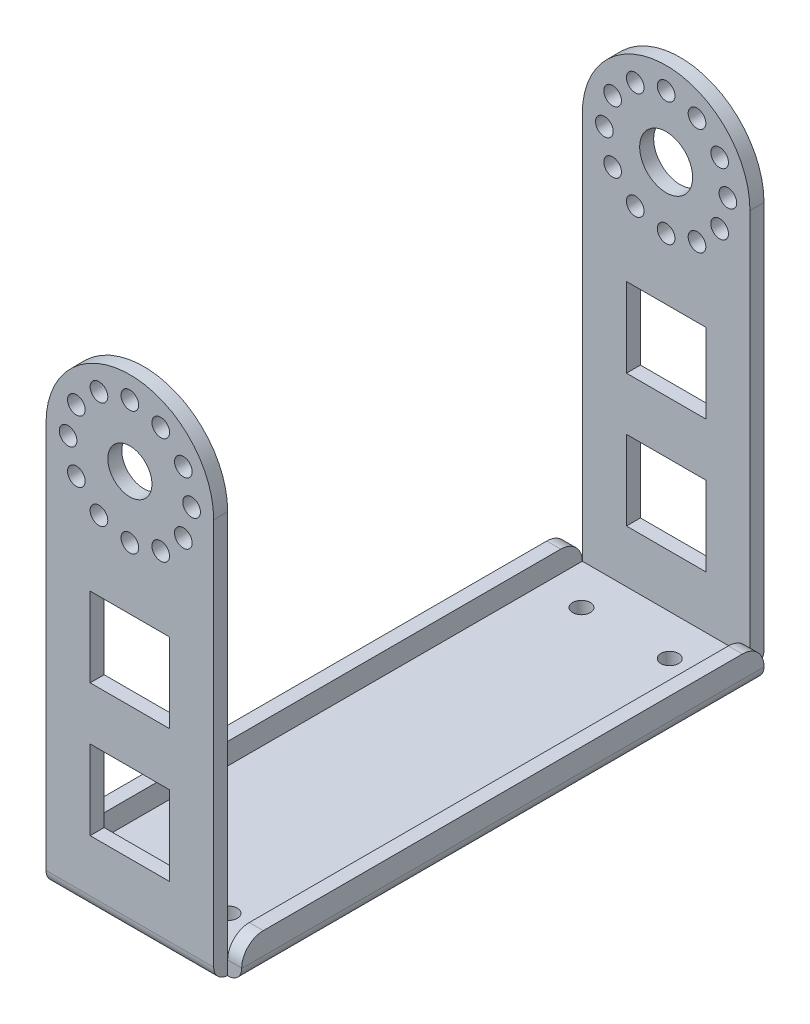
SolidWorks part; units mm, degrees
ref_plane "Plan de face" through (0, 0, 0) normal (0, 0, 1) x (1, 0, 0)
ref_plane "Plan de dessus" through (0, 0, 0) normal (0, 1, 0) x (1, 0, 0)
ref_plane "Plan de droite" through (0, 0, 0) normal (1, 0, 0) x (0, 0, -1)
sketch "Esquisse1" plane through (0, 0, 0) normal (0, 1, 0) x (1, 0, 0)
  line L1 (-9.5, -29.5938) -> (9.5, -29.5938)
  line L2 (-9.5, -29.5938) -> (-9.5, 29.5937)
  line L3 (-9.5, 29.5937) -> (9.5, 29.5937)
  line L4 (9.5, -29.5938) -> (9.5, 29.5937)
  line L5 (-9.5, -29.5938) -> (9.5, 29.5937) construction
  line L6 (-9.5, 29.5937) -> (9.5, -29.5938) construction
  point P0 (0, 0)
  dimension "D1" = 59.1875
  dimension "D2" = 19
extrude "Boss.-Extru.1" add sketch "Esquisse1" along normal blind 1.5875
sketch "Esquisse3" plane through (9.5, 0, 0) normal (1, 0, 0) x (0, 0, -1)
  line L1 (-29.5938, 0) -> (29.5937, 0)
  line L2 (-29.5938, 0) -> (-29.5938, 4)
  line L3 (-29.5938, 4) -> (29.5937, 4)
  line L4 (29.5937, 0) -> (29.5937, 4)
  dimension "D1" = 59.1875
  dimension "D2" = 4
extrude "Boss.-Extru.2" add sketch "Esquisse3" along normal blind 1.5875
sketch "Esquisse4" plane through (-9.5, 0, 0) normal (-1, 0, 0) x (0, 0, 1)
  line L1 (-29.5937, 0) -> (29.5938, 0)
  line L2 (-29.5937, 0) -> (-29.5937, 4)
  line L3 (-29.5937, 4) -> (29.5938, 4)
  line L4 (29.5938, 0) -> (29.5938, 4)
  dimension "D1" = 59.1875
  dimension "D2" = 4
extrude "Boss.-Extru.3" add sketch "Esquisse4" along normal blind 1.5875
fillet "Congé1" radius 1.5 1 edges at (11.0875, 0, 0)
fillet "Congé2" radius 1.5 1 edges at (-11.0875, 0, 0)
sketch "Esquisse5" plane through (0, 0, 29.5938) normal (0, 0, 1) x (1, 0, 0)
  line L1 (-9.5, 0.043) -> (9.5, 0.043)
  line L2 (-9.5, 0.043) -> (-9.5, 45.543)
  line L3 (-9.5, 45.543) -> (9.5, 45.543) construction
  line L4 (9.5, 0.043) -> (9.5, 45.543)
  circle A0 centre (0, 45.543) radius 2.5
  arc A1 (-9.5, 45.543) -> (9.5, 45.543) centre (0, 45.543) cw
  circle A2 centre (0, 45.543) radius 7 construction
  circle A3 centre (0, 38.543) radius 1
  circle A4 centre (-3.5, 39.4808) radius 1
  circle A5 centre (-6.0622, 42.043) radius 1
  circle A6 centre (-7, 45.543) radius 1
  circle A7 centre (-6.0622, 49.043) radius 1
  circle A8 centre (-3.5, 51.6052) radius 1
  circle A9 centre (0, 52.543) radius 1
  circle A10 centre (3.5, 51.6052) radius 1
  circle A11 centre (6.0622, 49.043) radius 1
  circle A12 centre (7, 45.543) radius 1
  circle A13 centre (6.0622, 42.043) radius 1
  circle A14 centre (3.5, 39.4808) radius 1
  point P33 (0, 45.543)
  dimension "D3" = 9.5
  dimension "D4" = 5
  dimension "D1" = 19
  dimension "D2" = 45.5
extrude "Boss.-Extru.8" add sketch "Esquisse5" along normal blind 1.5875 separate body
fillet "Congé3" radius 1.5875 3 edges at (0, 0.043, 31.1813) (9.5, 0.043, 30.3875) (-9.5, 0.043, 30.3875)
sketch "Esquisse8" plane through (0, 0, -29.5937) normal (0, 0, -1) x (-1, 0, 0)
  line L0 (-9.5875, 0) -> (9.5875, 0) construction
  line L1 (-9.5, 0) -> (9.5047, 0)
  line L2 (-9.5, 0) -> (-9.5, 45.5)
  line L3 (-9.5, 45.5) -> (9.5047, 45.5) construction
  line L4 (9.5047, 0) -> (9.5047, 45.5)
  arc A0 (9.5047, 45.5) -> (-9.5, 45.5) centre (0.0024, 45.5) ccw
  circle A1 centre (0.0024, 45.5) radius 3
  circle A2 centre (0.0024, 45.5) radius 7 construction
  circle A3 centre (0.0024, 38.5) radius 1
  circle A4 centre (-3.4976, 39.4378) radius 1
  circle A5 centre (-6.0598, 42) radius 1
  circle A6 centre (-6.9976, 45.5) radius 1
  circle A7 centre (-6.0598, 49) radius 1
  circle A8 centre (-3.4976, 51.5622) radius 1
  circle A9 centre (0.0024, 52.5) radius 1
  circle A10 centre (3.5024, 51.5622) radius 1
  circle A11 centre (6.0645, 49) radius 1
  circle A12 centre (7.0024, 45.5) radius 1
  circle A13 centre (6.0645, 42) radius 1
  circle A14 centre (3.5024, 39.4378) radius 1
  point P36 (0.0024, 45.5)
  dimension "D3" = 9.5024
  dimension "D1" = 19.0047
  dimension "D2" = 45.5
extrude "Boss.-Extru.10" add sketch "Esquisse8" along normal blind 1.5875 separate body
fillet "Congé4" radius 1.5875 3 edges at (-0.0024, 0, -31.1812) (-9.5047, 0, -30.3875) (9.5, 0, -30.3875)
sketch "Esquisse9" plane through (0, 1.5875, 0) normal (0, 1, 0) x (1, 0, 0)
  line L0 (0, -25) -> (0, -29.5938) construction
  line L1 (5, 25) -> (-5, 25) construction
  line L2 (5, 25) -> (5, -25) construction
  line L3 (5, -25) -> (-5, -25) construction
  line L4 (-5, 25) -> (-5, -25) construction
  line L5 (5, 25) -> (-5, -25) construction
  line L6 (5, -25) -> (-5, 25) construction
  line L7 (-9.5, -29.5938) -> (9.5, -29.5938) construction
  line L8 (-5, -3.1455) -> (-9.5, -3.1455) construction
  line L9 (-9.5, 29.5937) -> (-9.5, -29.5938) construction
  line L10 (5, -3.1455) -> (9.5, -3.1455) construction
  line L11 (9.5, -29.5938) -> (9.5, 29.5937) construction
  line L12 (0, 25) -> (0, 29.5937) construction
  line L13 (9.5, 29.5937) -> (-9.5, 29.5937) construction
  circle A0 centre (-5, 25) radius 1
  circle A1 centre (5, 25) radius 1
  circle A2 centre (-5, -25) radius 1
  circle A3 centre (5, -25) radius 1
  point P0 (0, 0)
  dimension "D3" = 2
  dimension "D1" = 50
  dimension "D2" = 10
extrude "Enlèv. mat.-Extru.1" cut sketch "Esquisse9" against normal blind 1.5875
sketch "Esquisse10" plane through (0, 0, 31.1813) normal (0, 0, 1) x (1, 0, 0)
  line L0 (4.5, 27.043) -> (9.5, 27.043) construction
  line L1 (-4.5, 22.543) -> (4.5, 22.543)
  line L2 (-4.5, 22.543) -> (-4.5, 31.543)
  line L3 (-4.5, 31.543) -> (4.5, 31.543)
  line L4 (4.5, 22.543) -> (4.5, 31.543)
  line L5 (-4.5, 22.543) -> (4.5, 31.543) construction
  line L6 (-4.5, 31.543) -> (4.5, 22.543) construction
  line L7 (9.5, 1.6305) -> (9.5, 45.543) construction
  line L8 (-4.5, 27.043) -> (-9.5, 27.043) construction
  line L9 (-9.5, 45.543) -> (-9.5, 1.6305) construction
  line L10 (0, 37.543) -> (0, 31.543) construction
  line L11 (0, 22.543) -> (0, 16.543) construction
  line L12 (4.5, 16.543) -> (-4.5, 16.543)
  line L13 (4.5, 16.543) -> (4.5, 7.543)
  line L14 (4.5, 7.543) -> (-4.5, 7.543)
  line L15 (-4.5, 16.543) -> (-4.5, 7.543)
  line L16 (-4.5, 16.543) -> (4.5, 7.543) construction
  line L17 (-4.5, 7.543) -> (4.5, 16.543) construction
  line L18 (4.5, 12.043) -> (9.5, 12.043) construction
  line L20 (-4.5, 12.043) -> (-9.5, 12.043) construction
  circle A0 centre (0, 38.543) radius 1 construction
  dimension "D1" = 5
  dimension "D2" = 6
  dimension "D3" = 6
extrude "Enlèv. mat.-Extru.2" cut sketch "Esquisse10" against normal through all
fillet "Congé5" radius 2.45 6 edges at (10.2937, 4, 29.5938) (-10.2938, 4, 29.5938)
fillet "Congé6" radius 2.45 6 edges at (10.2937, 4, -29.5937) (-10.2938, 4, -29.5937)
